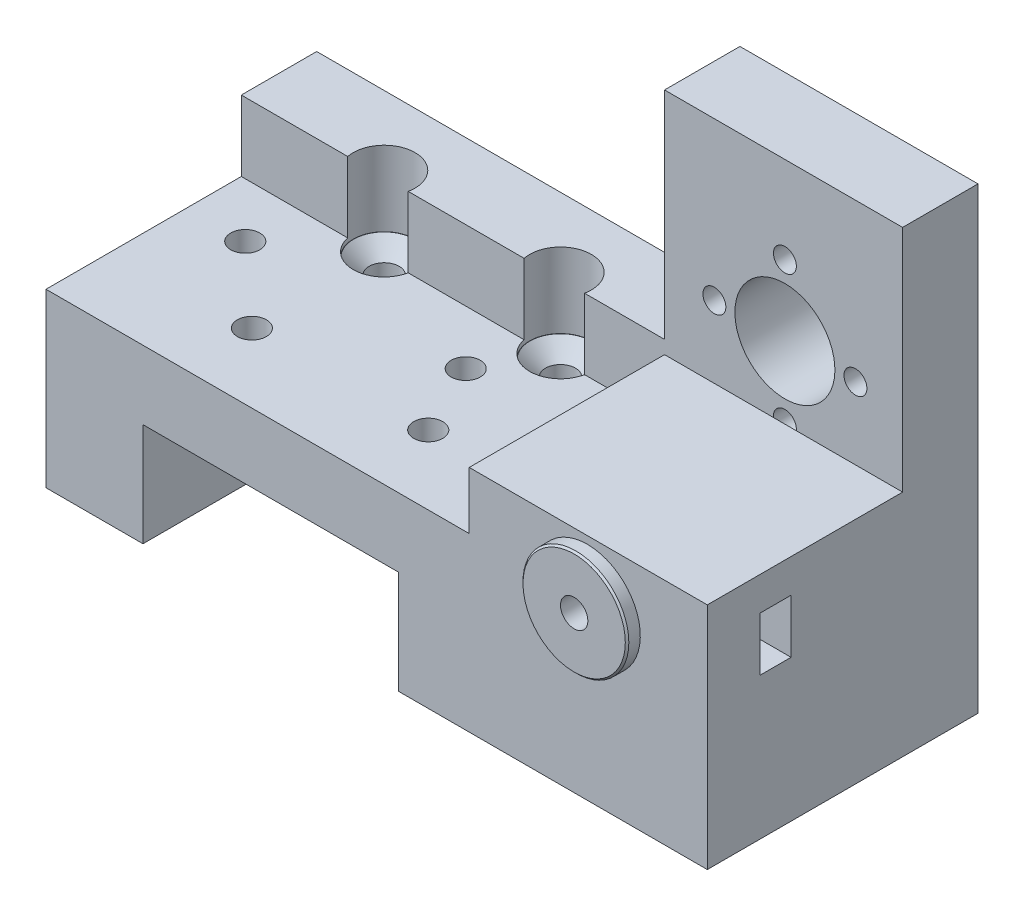
SolidWorks part; units mm, degrees
ref_plane "Front Plane" through (0, 0, 0) normal (0, 0, 1) x (1, 0, 0)
ref_plane "Top Plane" through (0, 0, 0) normal (0, 1, 0) x (1, 0, 0)
ref_plane "Right Plane" through (0, 0, 0) normal (1, 0, 0) x (0, 0, -1)
sketch "Croquis2" plane through (0, 0, 0) normal (0, 0, 1) x (1, 0, 0)
  line L0 (-42.15, -32.65) -> (-49.65, -32.65) construction
  line L1 (-42.15, -32.65) -> (-49.65, -32.65) construction
  line L2 (-49.65, -22.65) -> (-49.65, -32.65) construction
  line L3 (-49.65, -22.65) -> (-49.65, -32.65) construction
  line L5 (-61.65, -34.15) -> (13.35, -34.15)
  line L6 (-61.65, -34.15) -> (-61.65, 17.85)
  line L7 (-61.65, 17.85) -> (13.35, 17.85)
  line L8 (13.35, -34.15) -> (13.35, 17.85)
  line L9 (-50.65, -22.65) -> (-50.65, -22.45)
  line L10 (-21.65, -22.65) -> (-21.65, -32.65)
  line L11 (-21.65, -22.65) -> (-21.65, -34.15)
  line L13 (-50.65, -22.45) -> (-49.65, -22.45)
  line L14 (-21.65, -22.65) -> (-21.65, -22.45)
  line L15 (-21.65, -22.45) -> (-22.65, -22.45)
  line L16 (-50.65, -34.15) -> (-21.65, -34.15)
  line L17 (-30.45, -36.15) -> (-41.85, -36.15) construction
  line L18 (-49.65, -22.45) -> (-22.65, -22.45)
  line L19 (-49.65, -22.45) -> (-22.65, -22.45)
  line L28 (-50.65, -22.65) -> (-50.65, -32.65)
  line L29 (-50.65, -22.65) -> (-50.65, -34.15)
  circle A2 centre (0, 0) radius 5.67
  circle A3 centre (0, 0) radius 5.67
  circle A5 centre (0, 8) radius 1.3
  circle A6 centre (0, 8) radius 1.3
  circle A8 centre (8, 0) radius 1.3
  circle A9 centre (8, 0) radius 1.3
  circle A11 centre (0, -8) radius 1.3
  circle A12 centre (0, -8) radius 1.3
  circle A14 centre (-8, 0) radius 1.3
  circle A15 centre (-8, 0) radius 1.3
  circle M7 centre (0, 8) radius 1.6
  circle M8 centre (0, -8) radius 1.6
  circle M9 centre (8, 0) radius 1.6
  circle M10 centre (-8, 0) radius 1.6
  circle M12 centre (0, 0) radius 10.875
  dimension "D6" = 12
  dimension "D7" = 75
  dimension "D8" = 52
  dimension "D12" = 2
  dimension "D1" = 0.5
  dimension "D2" = 0.3
  dimension "D3" = 0.3
  dimension "D4" = 0.3
  dimension "D5" = 0.3
  dimension "D9" = 0.2
  dimension "D10" = 1
  dimension "D11" = 1
extrude "Saliente-Extruir1" add sketch "Croquis2" along normal offset from surface (30.7 mm away) 2 contours L29 L9 L13 L19 L15 L14 L11 L5 L8 L7 L6 M12 | A3 M12 M8 M10 M9 M7 | A6 M7 | A9 M9 | A12 M8 | A15 M10 region at (-25.6868, -6.9557, 0) region at (-1.5547, 8, 0) region at (-1.5547, -8, 0) region at (6.4453, 0, 0) region at (-9.5547, 0, 0) region at (-10.5674, 0, 0)
sketch "Croquis4" plane through (0, 0, 30.7) normal (0, 0, 1) x (1, 0, 0)
  line L0 (-61.65, 17.85) -> (13.35, 17.85) construction
  line L1 (-13.65, 17.85) -> (13.35, 17.85)
  line L2 (-13.65, 17.85) -> (-13.65, -8.15)
  line L3 (-13.65, -8.15) -> (13.35, -8.15)
  line L4 (13.35, 17.85) -> (13.35, -8.15)
  line L5 (13.35, -34.15) -> (13.35, 17.85) construction
  dimension "D1" = 27
  dimension "D2" = 26
extrude "Cortar-Extruir2" cut sketch "Croquis4" against normal offset from surface (22.7 mm away) 8 up to face at (-30.15, -18.225, 0)
sketch "Croquis6" plane through (0, 0, 30.7) normal (0, 0, 1) x (1, 0, 0)
  line L0 (-30.15, -32.65) -> (-30.15, -28.15) construction
  line L1 (-21.65, -34.15) -> (-50.65, -34.15)
  line L2 (-21.65, -34.15) -> (-21.65, -22.45)
  line L3 (-21.65, -22.45) -> (-50.65, -22.45)
  line L4 (-50.65, -34.15) -> (-50.65, -22.45)
  line L5 (-30.15, -28.15) -> (-42.15, -28.15) construction
  line L6 (-42.15, -28.15) -> (-42.15, -32.65) construction
  line L7 (-29.65, -34.15) -> (-29.65, -27.65)
  line L8 (-29.65, -27.65) -> (-42.65, -27.65)
  line L9 (-42.65, -27.65) -> (-42.65, -34.15)
  line L10 (-29.65, -32.65) -> (-29.65, -27.65) construction
  line L11 (-42.65, -27.65) -> (-42.65, -32.65) construction
  dimension "D1" = 0.5
sketch "Croquis3" plane through (-61.65, 0, 0) normal (-1, 0, 0) x (0, 0, 1)
  line L0 (-2, -22.65) -> (32.7, -22.65) construction
  line L1 (20.85, -14.65) -> (8.55, -14.65)
  line L2 (20.85, -14.65) -> (20.85, -6.65)
  line L3 (20.85, -6.65) -> (8.55, -6.65)
  line L4 (8.55, -14.65) -> (8.55, -6.65)
  line L5 (0, -34.15) -> (0, 17.85) construction
  line L6 (30.7, 17.85) -> (30.7, -34.15) construction
  dimension "D1" = 8
  dimension "D2" = 12.3
  dimension "D3" = 8
  dimension "D4" = 9.85
  dimension "D5" = 8.55
extrude "Cortar-Extruir5" cut sketch "Croquis3" against normal blind 43
sketch "Croquis5" plane through (0, 17.85, 0) normal (0, 1, 0) x (1, 0, 0)
  line L2 (-61.65, -14.7) -> (-11.635, -14.7) construction
  line L4 (-61.65, -8.55) -> (-61.65, -20.85) construction
  line L5 (-61.65, -8.55) -> (-61.65, -20.85)
  circle A2 centre (-55.05, -14.7) radius 1.75 construction
  circle A3 centre (-55.05, -14.7) radius 1.75 construction
  circle A4 centre (-30.05, -14.7) radius 1.75 construction
  circle A5 centre (-30.05, -14.7) radius 1.75 construction
  circle A6 centre (-55.05, -14.7) radius 1.65
  circle A7 centre (-30.05, -14.7) radius 1.65
  dimension "D1" = 3.3
extrude "Cortar-Extruir6" cut sketch "Croquis5" against normal through all contours L2 | L2 | L2 | L2 | A6 | A7 region at (-55.05, 17.85, 14.7) region at (-30.05, 17.85, 14.7)
sketch "Croquis7" plane through (0, 17.85, 0) normal (0, 1, 0) x (1, 0, 0)
  line L0 (-61.65, 0) -> (13.35, 0) construction
  line L1 (-61.65, -30.7) -> (-13.65, -30.7)
  line L2 (-61.65, -30.7) -> (-61.65, 0)
  line L3 (-61.65, 0) -> (-13.65, 0)
  line L4 (-13.65, -30.7) -> (-13.65, 0)
  line L5 (-61.65, -8.55) -> (-61.65, -20.85) construction
  line L6 (-61.65, -8.55) -> (-61.65, -20.85)
  line L8 (-61.65, -20.85) -> (-13.65, -20.85)
  line L9 (-61.65, -20.85) -> (-61.65, -30.7)
  line L10 (-61.65, -30.7) -> (-13.65, -30.7)
  line L11 (-13.65, -20.85) -> (-13.65, -30.7)
  line M3 (-13.65, -30.7) -> (-13.65, -8)
  line M6 (13.35, 0) -> (-61.65, 0)
  line M7 (-61.65, 0) -> (-61.65, -30.7)
  line M8 (-61.65, -30.7) -> (-13.65, -30.7)
  dimension "D1" = 48
extrude "Cortar-Extruir7" cut sketch "Croquis7" against normal up to surface (24.5 mm away) contours L2 L8 L4 M6 M7 | L8 M7 M8 M3 region at (-37.65, 17.85, 25.775) region at (-37.65, 17.85, 10.425)
sketch "Croquis11" plane through (0, -14.65, 0) normal (0, 1, 0) x (1, 0, 0)
  line L1 (-51.5859, -14.7) -> (-53.3179, -11.7)
  line L2 (-53.3179, -11.7) -> (-56.7821, -11.7)
  line L3 (-56.7821, -11.7) -> (-58.5141, -14.7)
  line L4 (-58.5141, -14.7) -> (-56.7821, -17.7)
  line L5 (-56.7821, -17.7) -> (-53.3179, -17.7)
  line L6 (-53.3179, -17.7) -> (-51.5859, -14.7)
  line L7 (-26.5859, -14.7) -> (-28.3179, -11.7)
  line L8 (-28.3179, -11.7) -> (-31.7821, -11.7)
  line L9 (-31.7821, -11.7) -> (-33.5141, -14.7)
  line L10 (-33.5141, -14.7) -> (-31.7821, -17.7)
  line L11 (-31.7821, -17.7) -> (-28.3179, -17.7)
  line L12 (-28.3179, -17.7) -> (-26.5859, -14.7)
  circle A0 centre (-46.15, -7.85) radius 1.5 construction
  circle A1 centre (-26.15, -7.85) radius 1.5 construction
  circle A2 centre (-26.15, -22.85) radius 1.5 construction
  circle A3 centre (-46.15, -22.85) radius 1.5 construction
  circle A4 centre (-46.15, -7.85) radius 1.5 construction
  circle A5 centre (-26.15, -7.85) radius 1.5 construction
  circle A6 centre (-26.15, -22.85) radius 1.5 construction
  circle A7 centre (-46.15, -22.85) radius 1.5 construction
  circle A8 centre (-46.15, -7.85) radius 3.5
  circle A9 centre (-26.15, -7.85) radius 3.5
  circle A10 centre (-26.15, -22.85) radius 3.5
  circle A11 centre (-46.15, -22.85) radius 3.5
  circle A12 centre (-55.05, -14.7) radius 3 construction
  circle A13 centre (-30.05, -14.7) radius 3 construction
  circle A14 centre (-46.15, -7.85) radius 1.65
  circle A15 centre (-26.15, -7.85) radius 1.65
  circle A16 centre (-26.15, -22.85) radius 1.65
  circle A17 centre (-46.15, -22.85) radius 1.65
  line M18 (-18.65, -8.55) -> (-61.65, -8.55)
  dimension "D1" = 7
  dimension "D2" = 6
  dimension "D3" = 3.3
extrude "Cortar-Extruir9" cut sketch "Croquis11" against normal offset from surface (8.5 mm away) 0.5 from surface contours A14 A8 M18 | A14 A8 L1 L6 M18 | A14 M18 | A14 M18 | A15 A9 M18 | A15 M18 | A15 M18 | A15 A9 M18 region at (-42.7489, -14.65, 8.1936) region at (-26.4936, -14.65, 4.4489) region at (-26.15, -14.65, 9.849) region at (-46.15, -14.65, 9.849) region at (-46.15, -14.65, 8.9413) region at (-46.15, -14.65, 7.5087) region at (-26.15, -14.65, 8.9413) region at (-26.15, -14.65, 7.5087) up to face at (-55.05, -14.65, 13.05) offset beyond the face yes starting at face at (-36.0944, -6.65, 14.2444)
extrude "Cortar-Extruir10" cut sketch "Croquis11<3>" against normal through all and the other way through all contours A14 M18 | A14 M18 | A15 M18 | A15 M18 | A16 | A17 region at (-46.15, -14.65, 8.9413) region at (-46.15, -14.65, 7.5087) region at (-26.15, -14.65, 8.9413) region at (-26.15, -14.65, 7.5087) region at (-26.15, -14.65, 22.85) region at (-46.15, -14.65, 22.85)
sketch "Croquis11<3>" plane through (0, -14.65, 0) normal (0, 1, 0) x (1, 0, 0) same geometry as "Croquis11"
extrude "Cortar-Extruir11" cut sketch "Croquis11<4>" along normal blind 3 and the other way through all from surface contours L11 L12 L7 L8 L9 L10 | L1 A8 L6 region at (-55.05, -14.65, 14.7) region at (-30.05, -14.65, 14.7) starting at face at (-46.15, -22.45, 24.5)
sketch "Croquis11<4>" plane through (0, -14.65, 0) normal (0, 1, 0) x (1, 0, 0) same geometry as "Croquis11"
hole_wizard "Avellanado para tornillo con cabeza avellanada de clavija hexagonal de M31" positions "Croquis16" profile "Croquis17" countersink size "M3" standard "DIN" end condition through all
sketch "Croquis16" plane through (0, -15.15, 0) normal (0, 1, 0) x (1, 0, 0)
  point P0 (-46.15, -7.85)
  point P3 (-26.15, -7.85)
sketch "Croquis17" plane through (-46.15, -15.15, 7.85) normal (1, 0, 0) x (0, 0, 1)
  line L0 (0, 0) -> (0, 19)
  line L1 (0, 19) -> (1.7, 19)
  line L2 (1.7, 19) -> (1.7, 1.77)
  line L3 (1.7, 1.77) -> (3.47, 0)
  line L5 (3.47, 0) -> (0, 0)
  line L6 (-1.7, 1.77) -> (-3.47, 0) construction
  line L11 (0, -6.35) -> (0, 107.95) construction
  dimension "Diámetro de taladro hasta el siguiente" = 3.4
  dimension "Profundidad de taladro hasta el siguiente" = 19
  dimension "Diámetro de avellanado cercano" = 6.94
  dimension "Ángulo de avellanado cercano" = 90
sketch "Croquis18" plane through (0, -6.65, 0) normal (0, 1, 0) x (1, 0, 0)
  line L1 (-61.65, -20.85) -> (-13.65, -20.85)
  line L2 (-61.65, -20.85) -> (-61.65, -30.7)
  line L3 (-61.65, -30.7) -> (-13.65, -30.7)
  line L4 (-13.65, -20.85) -> (-13.65, -30.7)
extrude "Cortar-Extruir12" cut sketch "Croquis18" against normal up to surface (8 mm away) up to face at (-38.15, -14.65, 12.325)
sketch "Croquis19" plane through (-18.65, 0, 0) normal (-1, 0, 0) x (0, 0, 1)
  line L4 (20.85, -14.65) -> (20.85, -6.65)
  line L5 (20.85, -6.65) -> (8.55, -6.65)
  line L6 (8.55, -6.65) -> (8.55, -14.65)
  line L7 (8.55, -14.65) -> (20.85, -14.65)
  line L8 (20.85, -14.65) -> (20.85, -6.65)
  line L9 (20.85, -6.65) -> (8.55, -6.65)
  line L10 (8.55, -6.65) -> (8.55, -14.65)
  line L11 (8.55, -14.65) -> (20.85, -14.65)
  dimension "D1" = 0
extrude "Cortar-Extruir13" cut sketch "Croquis19" against normal up to surface (5 mm away) up to face at (-13.65, -11.4, 25.775)
sketch "Croquis20" plane through (0, 0, 8) normal (0, 0, 1) x (1, 0, 0)
  line L5 (-13.65, -6.65) -> (-13.65, -8.15)
  line L6 (-13.65, -8.15) -> (-1.2913, -8.15)
  line L7 (13.35, -8.15) -> (13.35, 17.85)
  line L8 (13.35, 17.85) -> (-13.65, 17.85)
  line L9 (-13.65, 17.85) -> (-13.65, -6.65)
  line L11 (-13.65, -8.15) -> (-1.2913, -8.15)
  line L12 (13.35, -8.15) -> (13.35, 17.85)
  line L13 (13.35, 17.85) -> (-13.65, 17.85)
  line L14 (-13.65, 17.85) -> (-13.65, -6.65)
  line L18 (-13.65, -6.65) -> (-13.65, -8.15)
  line L19 (1.2913, -8.15) -> (13.35, -8.15)
  line L20 (1.2913, -8.15) -> (13.35, -8.15)
  circle A0 centre (-8, 0) radius 1.3 construction
  circle A1 centre (-8, 0) radius 1.3
  circle A2 centre (0, -8) radius 1.3 construction
  circle A3 centre (8, 0) radius 1.3 construction
  circle A4 centre (0, 8) radius 1.3 construction
  circle A5 centre (0, -8) radius 1.3
  circle A6 centre (8, 0) radius 1.3
  circle A7 centre (0, 8) radius 1.3
  circle A8 centre (0, 0) radius 5.67 construction
  circle A9 centre (0, 0) radius 5.67
  arc A11 (1.2913, -8.15) -> (-1.2913, -8.15) centre (0, -8) ccw
  arc A14 (1.2913, -8.15) -> (-1.2913, -8.15) centre (0, -8) ccw
  circle M6 centre (-8, 0) radius 1.3
  circle M7 centre (8, 0) radius 1.3
  circle M8 centre (0, 8) radius 1.3
  circle M9 centre (0, 0) radius 5.67
  arc M10 (-1.2913, -8.15) -> (1.2913, -8.15) centre (0, -8) cw
  line M11 (-13.65, -6.65) -> (-13.65, -8.15)
  line M12 (-13.65, -8.15) -> (-1.2913, -8.15)
  line M13 (13.35, -8.15) -> (13.35, 17.85)
  line M14 (13.35, 17.85) -> (-13.65, 17.85)
  line M15 (-13.65, 17.85) -> (-13.65, -6.65)
  line M21 (1.2913, -8.15) -> (13.35, -8.15)
  dimension "D1" = 0
extrude "Saliente-Extruir2" add sketch "Croquis20" along normal up to surface (0.55 mm away) contours M10 M21 M13 M14 M15 M11 M12 M7 M9 M8 M6 region at (-0.1809, 5.8161, 8) up to face at (-17.2783, -10.15, 8.55)
sketch "Croquis22" plane through (0, 0, 30.7) normal (0, 0, 1) x (1, 0, 0)
  line L0 (-1.2913, -8.15) -> (1.2913, -8.15)
  arc A0 (-1.2913, -8.15) -> (1.2913, -8.15) centre (0, -8) ccw construction
  arc A1 (-1.2913, -8.15) -> (1.2913, -8.15) centre (0, -8) ccw
extrude "Saliente-Extruir4" add sketch "Croquis22" against normal up to surface (22.15 mm away) up to face at (-36.15, -10.65, 8.55)
sketch "Croquis21" plane through (0, 0, 30.7) normal (0, 0, 1) x (1, 0, 0)
  line L0 (1.5109, -11.95) -> (13.35, -11.95)
  line L1 (-2.0109, -11.95) -> (-3.7718, -15)
  line L2 (-3.7718, -15) -> (-2.0109, -18.05)
  line L3 (-2.0109, -18.05) -> (1.5109, -18.05)
  line L4 (1.5109, -18.05) -> (3.2718, -15)
  line L5 (3.2718, -15) -> (1.5109, -11.95)
  line L6 (1.5109, -11.95) -> (-2.0109, -11.95)
  line L7 (13.35, -8.15) -> (13.35, -34.15) construction
  line L8 (1.5109, -18.05) -> (13.35, -18.05)
  line L9 (13.35, -18.05) -> (13.35, -11.95)
  circle A0 centre (-0.25, -15) radius 2.5 construction
  circle A1 centre (-0.25, -15) radius 2.5 construction
  circle A2 centre (-0.25, -15) radius 1.55
  circle A3 centre (-0.25, -15) radius 3.05 construction
  circle A5 centre (-0.25, -15) radius 6
  line M9 (13.35, -34.15) -> (13.35, -8.15)
  dimension "D1" = 3.1
  dimension "D2" = 6.1
  dimension "D3" = 12
extrude "Cortar-Extruir14" cut sketch "Croquis21" against normal blind 6 contours A2 region at (-0.25, -15, 30.7)
extrude "Cortar-Extruir15" cut sketch "Croquis21<4>" against normal blind 3.5 from surface contours A2 | L5 L6 L1 L2 L3 L4 A2 | A5 L8 L0 M9 | L8 A5 L0 L5 L4 region at (3.9039, -15, 30.7) region at (2.3107, -13.5216, 30.7) region at (9.4114, -15, 30.7) region at (-0.25, -15, 30.7) starting at face at (1.3, -15, 24.7)
sketch "Croquis21<4>" plane through (0, 0, 30.7) normal (0, 0, 1) x (1, 0, 0) same geometry as "Croquis21"
extrude "Cortar-Extruir16" cut sketch "Croquis21<5>" against normal blind 3 from surface contours A2 region at (-0.25, -15, 30.7) starting at face at (3.7813, -15, 21.2)
sketch "Croquis21<5>" plane through (0, 0, 30.7) normal (0, 0, 1) x (1, 0, 0) same geometry as "Croquis21"
extrude "Saliente-Extruir3" add sketch "Croquis21<6>" along normal blind 1.5 contours L0 A5 L8 L3 L2 L1 L6 | L8 A5 L0 L5 L4 | L5 L6 L1 L2 L3 L4 A2 region at (-0.25, -11.7861, 30.7) region at (3.9039, -15, 30.7) region at (2.3107, -13.5216, 30.7)
sketch "Croquis21<6>" plane through (0, 0, 30.7) normal (0, 0, 1) x (1, 0, 0) same geometry as "Croquis21"
chamfer "Chaflán1" distance 0.2 1 edges at (5.75, -15, 32.2)
